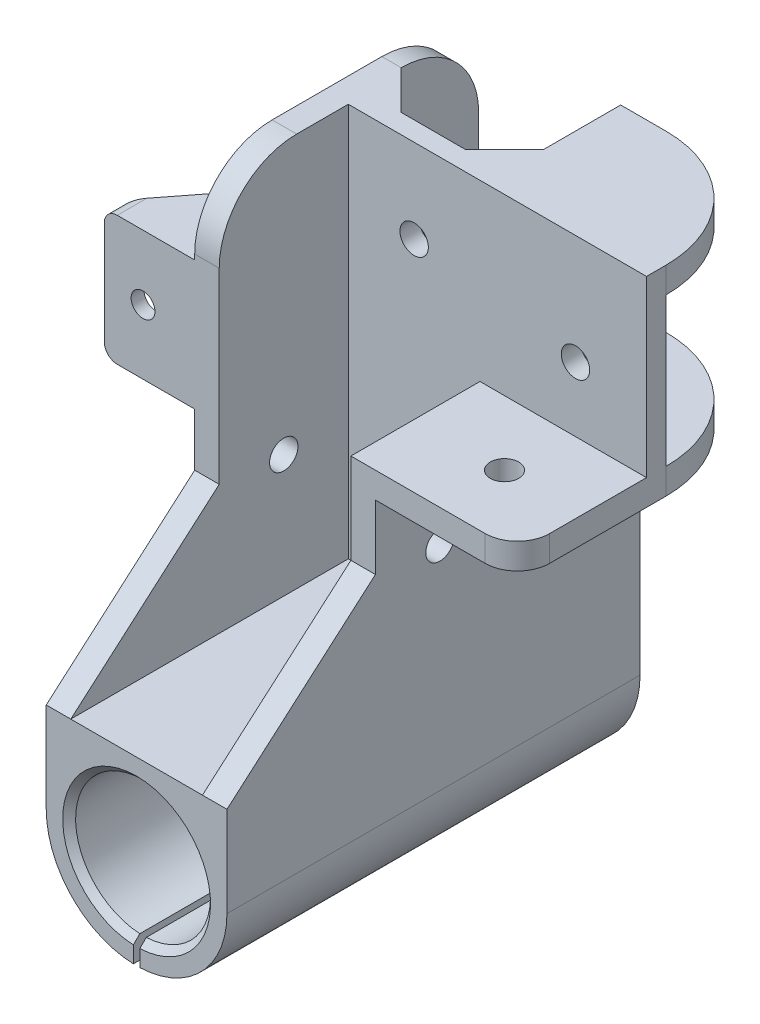
SolidWorks part; units mm, degrees
material "ABS"
ref_plane "Front Plane" through (0, 0, 0) normal (0, 0, 1) x (1, 0, 0)
ref_plane "Top Plane" through (0, 0, 0) normal (0, 1, 0) x (1, 0, 0)
ref_plane "Right Plane" through (0, 0, 0) normal (1, 0, 0) x (0, 0, -1)
sketch "Sketch1" plane through (0, 0, 0) normal (0, 0, 1) x (1, 0, 0)
  line L0 (-14, 0) -> (-14, 75)
  line L3 (-14, 75) -> (36, 75)
  line L4 (14, 44) -> (14, 0)
  line L5 (14, 44) -> (36, 44)
  line L6 (36, 44) -> (36, 75)
  arc A0 (-14, 0) -> (14, 0) centre (0, 0) ccw
  dimension "D3" = 28
  dimension "D1" = 31
  dimension "D4" = 75
  dimension "D5" = 22
extrude "Boss-Extrude1" add sketch "Sketch1" along normal blind 64
sketch "Sketch2" plane through (0, 75, 0) normal (0, 1, 0) x (1, 0, 0)
  line L0 (-11, 0) -> (-11, -12)
  line L1 (36, 0) -> (-14, 0) construction
  line L2 (-11, -12) -> (-5, -18)
  line L3 (-5, -18) -> (5, -18)
  line L4 (5, -18) -> (11, -12)
  line L5 (11, -12) -> (11, 0)
  line L6 (11, 0) -> (-11, 0)
  line L7 (14, -64) -> (14, 0) construction
  dimension "D1" = 10
  dimension "D2" = 22
  dimension "D3" = 3
  dimension "D4" = 12
  dimension "D5" = 18
extrude "Cut-Extrude1" cut sketch "Sketch2" against normal blind 61
sketch "Sketch3" plane through (14, 0, 0) normal (1, 0, 0) x (0, 0, -1)
  line L0 (-64, 14) -> (-41, 34)
  line L1 (-64, 0) -> (-64, 44) construction
  line L2 (-41, 34) -> (-41, 75)
  line L3 (-64, 75) -> (0, 75) construction
  line L4 (-41, 75) -> (-64, 75)
  line L5 (-64, 75) -> (-64, 14)
  dimension "D1" = 23
  dimension "D2" = 41
  dimension "D3" = 61
extrude "Cut-Extrude2" cut sketch "Sketch3" against normal through all both and the other way through all
sketch "Sketch4" plane through (0, 0, 64) normal (0, 0, 1) x (1, 0, 0)
  line L0 (-10.2, 14) -> (-10.2, 75)
  line L1 (-14, 14) -> (14, 14) construction
  line L2 (36, 44) -> (14, 44) construction
  line L4 (-14, 75) -> (36, 75) construction
  line L5 (-10.2, 75) -> (36, 75)
  line L7 (10.2, 48) -> (10.2, 14)
  line L8 (10.2, 14) -> (-10.2, 14)
  line L9 (-14, 14) -> (-14, 34) construction
  line L10 (14, 14) -> (14, 34) construction
  line L12 (10.2, 48) -> (36, 48)
  line L13 (36, 44) -> (36, 75) construction
  line L14 (36, 48) -> (36, 75)
  dimension "D1" = 3.8
  dimension "D2" = 3.8
  dimension "D3" = 4
extrude "Cut-Extrude3" cut sketch "Sketch4" against normal blind 43
sketch "Sketch5" plane through (0, 0, 64) normal (0, 0, 1) x (1, 0, 0)
  line L0 (0, -10.45) -> (0, -14) construction
  line L1 (-0.5, -10.438) -> (-0.5, -13.9911)
  line L2 (0.5, -10.438) -> (0.5, -13.9911)
  line L3 (-0.5, -10.45) -> (-0.5, -17.5466) construction
  line L4 (0, -10.45) -> (0, -17.5466) construction
  line L5 (0.5, -10.45) -> (0.5, -17.5466) construction
  arc A0 (0.5, -10.438) -> (-0.5, -10.438) centre (0, 0) ccw
  arc A1 (-14, 0) -> (14, 0) centre (0, 0) ccw construction
  arc A2 (-0.5, -13.9911) -> (0.5, -13.9911) centre (0, 0) ccw
  dimension "D1" = 20.9
  dimension "D2" = 0.5
  dimension "D3" = 0.5
extrude "Cut-Extrude4" cut sketch "Sketch5" against normal through all
chamfer "Chamfer1" distance 1 angle 45 2 edges at (0, 10.45, 0) (0, 10.45, 64)
sketch "Sketch6" plane through (0, 0, 21) normal (0, 0, 1) x (1, 0, 0)
  line L0 (0, 14) -> (0, 27) construction
  line L1 (-10.2, 14) -> (10.2, 14) construction
  line L4 (10.2, 48) -> (36, 48) construction
  line L5 (36, 48) -> (36, 75) construction
  circle A1 centre (0, 62) radius 2.2
  circle A2 centre (0, 27) radius 2.2
  circle A3 centre (25, 58) radius 2.2
  dimension "D1" = 4.4
  dimension "D2" = 35
  dimension "D7" = 11
  dimension "D3" = 13
  dimension "D6" = 10
extrude "Cut-Extrude5" cut sketch "Sketch6" against normal through all
sketch "Sketch7" plane through (-14, 0, 0) normal (1, 0, 0) x (0, 0, -1)
  line L0 (-41, 62.2) -> (-21, 62.2)
  line L1 (-41, 34) -> (-41, 44) construction
  line L2 (-21, 62.2) -> (-21, 60.2)
  line L3 (-21, 60.2) -> (-39, 60.2)
  line L4 (-39, 60.2) -> (-39, 44.2)
  line L5 (-39, 44.2) -> (-21, 44.2)
  line L6 (-21, 44.2) -> (-21, 42.2)
  line L7 (-21, 42.2) -> (-41, 42.2)
  line L8 (-41, 42.2) -> (-41, 62.2)
  line L9 (-41, 75) -> (0, 75) construction
  dimension "D1" = 20
  dimension "D2" = 12.8
  dimension "D3" = 2
  dimension "D4" = 2
extrude "Boss-Extrude2" add sketch "Sketch7" against normal blind 14
sketch "Sketch8" plane through (0, 62.2, 0) normal (0, 1, 0) x (1, 0, 0)
  line L0 (-14, -21) -> (-28, -39)
  line L1 (-28, -21) -> (-28, -41) construction
  line L2 (-28, -39) -> (-28, -21)
  line L3 (-28, -21) -> (-14, -21)
  line L5 (-28, -41) -> (-14, -41) construction
  dimension "D1" = 2
extrude "Cut-Extrude6" cut sketch "Sketch8" against normal through all
sketch "Sketch9" plane through (0, 0, 41) normal (0, 0, 1) x (1, 0, 0)
  line L0 (-22, 52.2) -> (-28, 52.2) construction
  line L1 (-28, 62.2) -> (-28, 42.2) construction
  line L2 (-28, 62.2) -> (-28, 42.2) construction
  circle A0 centre (-22, 52.2) radius 1.85
  dimension "D1" = 3.7
  dimension "D2" = 6
extrude "Cut-Extrude7" cut sketch "Sketch9" against normal through all
fillet "Fillet1" radius 2 2 edges at (-28, 42.2, 40) (-28, 62.2, 40)
fillet "Fillet2" radius 12 2 edges at (-12.1, 75, 41) (-12.5, 75, 0)
sketch "Sketch10" plane through (14, 0, 0) normal (1, 0, 0) x (0, 0, -1)
  line L0 (0, 0) -> (0, 44) construction
  line L2 (-21, 75) -> (-29, 75) construction
  circle A0 centre (-31, 33) radius 2.2
  dimension "D1" = 4.4
  dimension "D2" = 31
  dimension "D3" = 42
extrude "Cut-Extrude8" cut sketch "Sketch10" against normal through all
fillet "Fillet3" radius 5 1 edges at (36, 46, 41)
fillet "Fillet4" radius 18 1 edges at (36, 59.5, 0)
sketch "Sketch11" plane through (0, 48, 0) normal (0, 1, 0) x (1, 0, 0)
  line L2 (31, -41) -> (10.2, -41) construction
  line L3 (36, -21) -> (36, -36) construction
  circle A0 centre (24, -31) radius 2.2
  dimension "D1" = 4.4
  dimension "D3" = 10
  dimension "D2" = 12
extrude "Cut-Extrude9" cut sketch "Sketch11" against normal through all
sketch "Sketch12" plane through (36, 0, 0) normal (-1, 0, 0) x (0, 0, 1)
  line L1 (18, 71) -> (0, 71)
  line L2 (18, 71) -> (18, 48)
  line L3 (18, 48) -> (0, 48)
  line L4 (0, 71) -> (0, 48)
  line L8 (29, 75) -> (12, 75) construction
  line L9 (0, 63) -> (0, 0) construction
  dimension "D1" = 4
  dimension "D2" = 23
  dimension "D3" = 18
extrude "Cut-Extrude10" cut sketch "Sketch12" along normal blind 22
